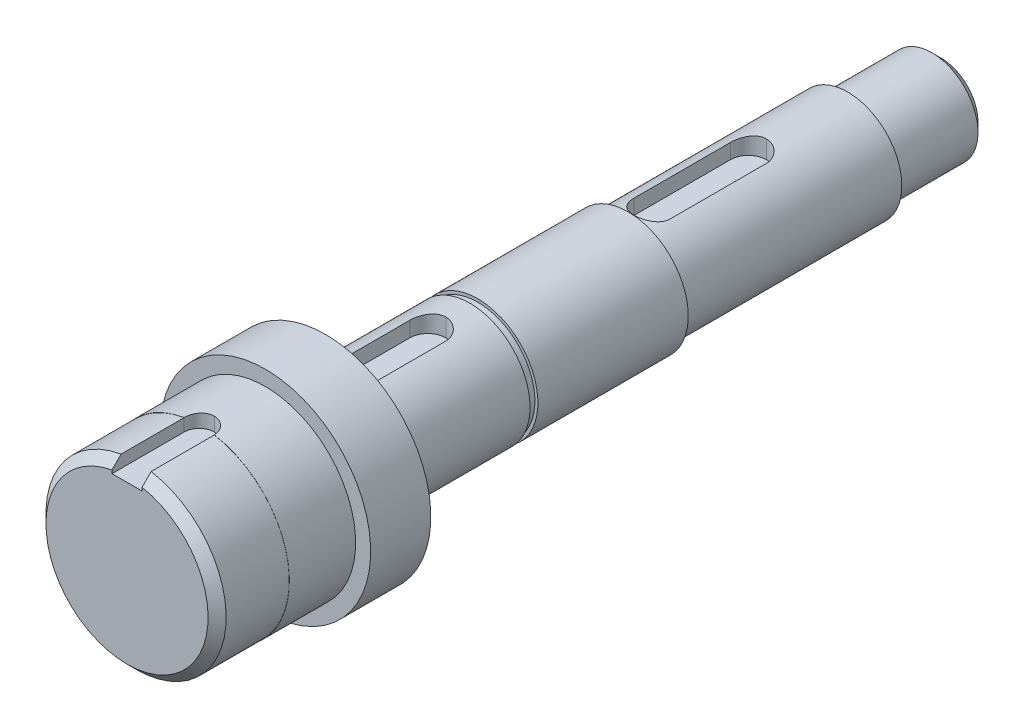
SolidWorks part; units mm, degrees
material "Plain Carbon Steel"
ref_plane "Front Plane" through (0, 0, 0) normal (0, 0, 1) x (1, 0, 0)
ref_plane "Top Plane" through (0, 0, 0) normal (0, 1, 0) x (1, 0, 0)
ref_plane "Right Plane" through (0, 0, 0) normal (1, 0, 0) x (0, 0, -1)
sketch "Sketch1" plane through (0, 0, 0) normal (0, 0, 1) x (1, 0, 0)
  circle A0 centre (0, 0) radius 14.975
  dimension "D1" = 29.95
extrude "Extrude1" add sketch "Sketch1" against normal blind 12
sketch "Sketch2" plane through (0, 0, -12) normal (0, 0, -1) x (-1, 0, 0)
  circle A0 centre (0, 0) radius 15
  dimension "D1" = 30
extrude "Extrude2" add sketch "Sketch2" along normal blind 11
sketch "Sketch3" plane through (0, 0, -23) normal (0, 0, -1) x (-1, 0, 0)
  circle A0 centre (0, 0) radius 17.5
  dimension "D1" = 35
extrude "Extrude3" add sketch "Sketch3" along normal blind 10
sketch "Sketch4" plane through (0, 0, -33) normal (0, 0, -1) x (-1, 0, 0)
  circle A0 centre (0, 0) radius 10
  dimension "D1" = 20
extrude "Extrude4" add sketch "Sketch4" along normal blind 24
sketch "Sketch5" plane through (0, 0, -57) normal (0, 0, -1) x (-1, 0, 0)
  circle A0 centre (0, 0) radius 9.5
  dimension "D1" = 19
extrude "Extrude5" add sketch "Sketch5" along normal blind 1.3
sketch "Sketch6" plane through (0, 0, -58.3) normal (0, 0, -1) x (-1, 0, 0)
  circle A0 centre (0, 0) radius 10
  dimension "D1" = 20
extrude "Extrude6" add sketch "Sketch6" along normal blind 25
sketch "Sketch7" plane through (0, 0, -83.3) normal (0, 0, -1) x (-1, 0, 0)
  circle A0 centre (0, 0) radius 9
  dimension "D1" = 18
extrude "Extrude7" add sketch "Sketch7" along normal blind 36.5
sketch "Sketch8" plane through (0, 0, -119.8) normal (0, 0, -1) x (-1, 0, 0)
  circle A0 centre (0, 0) radius 7.6602
extrude "Extrude8" add sketch "Sketch8" along normal blind 15.5
sketch "Sketch9" plane through (0, 0, 0) normal (0, 0, 1) x (1, 0, 0)
  line L1 (-2.5, 17.8852) -> (2.5, 17.8852)
  line L2 (-2.5, 17.8852) -> (-2.5, 12.7)
  line L3 (-2.5, 12.7) -> (2.5, 12.7)
  line L4 (2.5, 17.8852) -> (2.5, 12.7)
  circle A1 centre (0, 0) radius 15 construction
  dimension "D3" = 27.7
  dimension "D1" = 5
  dimension "D2" = 2.5
extrude "Cut-Extrude1" cut sketch "Sketch9" against normal blind 14.5
fillet "Fillet1" radius 2.5 2 edges at (2.5, 13.7451, -14.5) (-2.5, 13.7451, -14.5)
chamfer "Chamfer1" distance 1.5 angle 45 1 edges at (0, -14.975, 0)
ref_plane "Plane1" through (0, 10, 0) normal (0, 1, 0) x (-1, 0, 0)
sketch "Sketch10" plane through (0, 10, 0) normal (0, 1, 0) x (-1, 0, 0)
  line L0 (-10, -33) -> (10, -33) construction
  line L1 (-3, -35) -> (3, -35)
  line L2 (-3, -35) -> (-3, -53)
  line L3 (-3, -53) -> (3, -53)
  line L4 (3, -35) -> (3, -53)
  dimension "D1" = 6
  dimension "D2" = 3
  dimension "D3" = 2
  dimension "D4" = 18
extrude "Cut-Extrude2" cut sketch "Sketch10" against normal blind 3
fillet "Fillet2" radius 3 4 edges at (3, 8.2697, -53) (-3, 8.2697, -53) (-3, 8.2697, -35) (3, 8.2697, -35)
ref_plane "Plane2" through (0, 9, 0) normal (0, 1, 0) x (-1, 0, 0)
sketch "Sketch11" plane through (0, 9, 0) normal (0, 1, 0) x (-1, 0, 0)
  line L0 (-9, -83.3) -> (9, -83.3) construction
  line L1 (-3.0055, -84.3) -> (2.9968, -84.3)
  line L2 (-3.0055, -84.3) -> (-3.0055, -106.3)
  line L3 (-3.0055, -106.3) -> (2.9945, -106.3)
  line L4 (2.9968, -84.3) -> (2.9945, -106.3)
  dimension "D1" = 1
  dimension "D2" = 22
  dimension "D3" = 6
  dimension "D4" = 3
extrude "Cut-Extrude3" cut sketch "Sketch11" against normal blind 3
fillet "Fillet3" radius 3 4 edges at (-2.9945, 7.2436, -106.3) (3.0055, 7.2417, -106.3) (3.0055, 7.2417, -84.3) (-2.9968, 7.2432, -84.3)
chamfer "Chamfer2" distance 1.5 angle 45 1 edges at (-7.6602, 0, -135.3)
